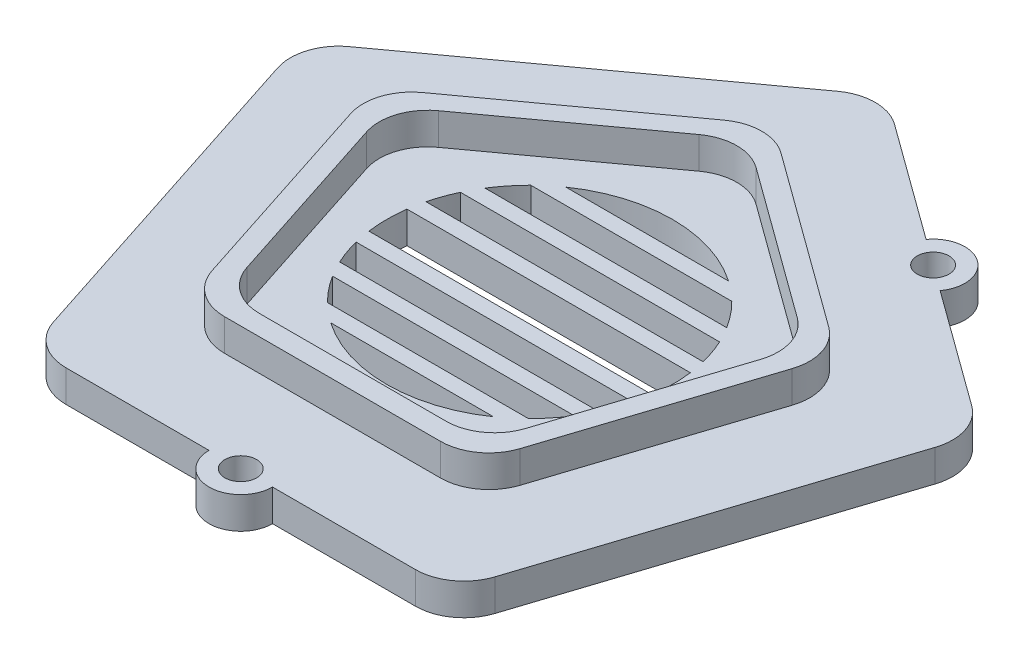
SolidWorks part; units mm, degrees
material "ABS"
ref_plane "Front Plane" through (0, 0, 0) normal (0, 0, 1) x (1, 0, 0)
ref_plane "Top Plane" through (0, 0, 0) normal (0, 1, 0) x (1, 0, 0)
ref_plane "Right Plane" through (0, 0, 0) normal (1, 0, 0) x (0, 0, -1)
sketch "Sketch1" plane through (0, 0, 0) normal (0, 1, 0) x (1, 0, 0)
  line L0 (-12.5926, 0) -> (122.24, 0) construction
  line L1 (-76.5046, 8.789) -> (-56.7275, -52.0787)
  line L2 (-32, -70.0442) -> (32, -70.0442)
  line L3 (56.7275, -52.0787) -> (76.5046, 8.789)
  line L4 (67.0595, 37.8578) -> (15.2824, 75.4761)
  line L5 (-15.2824, 75.4761) -> (-67.0595, 37.8578)
  line L7 (-72.7662, 7.5743) -> (-54.4171, -48.8987)
  line L8 (-29.6896, -66.8642) -> (29.6896, -66.8642)
  line L9 (54.4171, -48.8987) -> (72.7662, 7.5743)
  line L10 (63.3212, 36.6432) -> (15.2824, 71.5454)
  line L11 (-15.2824, 71.5454) -> (-63.3212, 36.6432)
  line L12 (-39.9799, 8.2808) -> (-27.4771, -30.1989)
  line L13 (-20.23, -35.4642) -> (20.23, -35.4642)
  line L14 (27.4771, -30.1989) -> (39.9799, 8.2808)
  line L15 (37.2118, 16.8002) -> (4.4789, 40.582)
  line L16 (-4.4789, 40.582) -> (-37.2118, 16.8002)
  line L17 (-34.7536, 6.5827) -> (-24.2471, -25.7532)
  line L18 (-17, -31.0185) -> (17, -31.0185)
  line L19 (24.2471, -25.7532) -> (34.7536, 6.5827)
  line L20 (31.9855, 15.1021) -> (4.4789, 35.0868)
  line L21 (-4.4789, 35.0868) -> (-31.9855, 15.1021)
  line L22 (-31.0153, 5.3681) -> (-21.9366, -22.5732)
  line L23 (-14.6896, -27.8385) -> (14.6896, -27.8385)
  line L24 (21.9366, -22.5732) -> (31.0153, 5.3681)
  line L25 (28.2472, 13.8875) -> (4.4789, 31.1561)
  line L26 (-4.4789, 31.1561) -> (-28.2472, 13.8875)
  circle A0 centre (0, 0) radius 70.0442 construction
  arc A1 (-56.7275, -52.0787) -> (-32, -70.0442) centre (-32, -44.0442) ccw
  arc A2 (32, -70.0442) -> (56.7275, -52.0787) centre (32, -44.0442) ccw
  arc A3 (76.5046, 8.789) -> (67.0595, 37.8578) centre (51.7771, 16.8234) ccw
  arc A4 (15.2824, 75.4761) -> (-15.2824, 75.4761) centre (0, 54.4417) ccw
  arc A5 (-76.5046, 8.789) -> (-67.0595, 37.8578) centre (-51.7771, 16.8234) cw
  circle A6 centre (0, 0) radius 66.8642 construction
  arc A7 (15.2824, 71.5454) -> (-15.2824, 71.5454) centre (0, 50.511) ccw
  arc A8 (72.7662, 7.5743) -> (63.3212, 36.6432) centre (48.0388, 15.6087) ccw
  arc A9 (29.6896, -66.8642) -> (54.4171, -48.8987) centre (29.6896, -40.8642) ccw
  arc A10 (-72.7662, 7.5743) -> (-63.3212, 36.6432) centre (-48.0388, 15.6087) cw
  arc A11 (-54.4171, -48.8987) -> (-29.6896, -66.8642) centre (-29.6896, -40.8642) ccw
  circle A12 centre (0, 0) radius 35.4642 construction
  circle A13 centre (0, 0) radius 31.0185 construction
  arc A14 (-24.2471, -25.7532) -> (-17, -31.0185) centre (-17, -23.3985) ccw
  arc A15 (17, -31.0185) -> (24.2471, -25.7532) centre (17, -23.3985) ccw
  arc A16 (34.7536, 6.5827) -> (31.9855, 15.1021) centre (27.5066, 8.9374) ccw
  arc A17 (4.4789, 35.0868) -> (-4.4789, 35.0868) centre (0, 28.9221) ccw
  arc A18 (4.4789, 40.582) -> (-4.4789, 40.582) centre (0, 34.4173) ccw
  arc A19 (39.9799, 8.2808) -> (37.2118, 16.8002) centre (32.7328, 10.6355) ccw
  arc A20 (20.23, -35.4642) -> (27.4771, -30.1989) centre (20.23, -27.8442) ccw
  arc A21 (-27.4771, -30.1989) -> (-20.23, -35.4642) centre (-20.23, -27.8442) ccw
  arc A22 (-39.9799, 8.2808) -> (-37.2118, 16.8002) centre (-32.7328, 10.6355) cw
  arc A23 (-34.7536, 6.5827) -> (-31.9855, 15.1021) centre (-27.5066, 8.9374) cw
  circle A24 centre (0, 0) radius 27.8385 construction
  arc A25 (-21.9366, -22.5732) -> (-14.6896, -27.8385) centre (-14.6896, -20.2185) ccw
  arc A26 (14.6896, -27.8385) -> (21.9366, -22.5732) centre (14.6896, -20.2185) ccw
  arc A27 (31.0153, 5.3681) -> (28.2472, 13.8875) centre (23.7683, 7.7228) ccw
  arc A28 (4.4789, 31.1561) -> (-4.4789, 31.1561) centre (0, 24.9914) ccw
  arc A29 (-31.0153, 5.3681) -> (-28.2472, 13.8875) centre (-23.7683, 7.7228) cw
  dimension "D1" = 26
  dimension "D3" = 26
  dimension "D5" = 7.62
  dimension "D8" = 7.62
  dimension "D2" = 64
  dimension "D4" = 3.18
  dimension "D6" = 40.46
  dimension "D7" = 34
  dimension "D9" = 3.18
extrude "Boss-Extrude1" add sketch "Sketch1" along normal blind 10 contours A23 L17 A14 L18 A15 L19 A16 L20 A17 L21 L22 A29 L26 A28 L25 A27 L24 A26 L23 A25 region at (-33.8267, 0, -10.9909)
sketch "Sketch2" plane through (0, 0, 0) normal (0, -1, 0) x (1, 0, 0)
  line L15 (-54.4171, 48.8987) -> (-72.7662, -7.5743)
  line L16 (29.6896, 66.8642) -> (-29.6896, 66.8642)
  line L17 (72.7662, -7.5743) -> (54.4171, 48.8987)
  line L18 (15.2824, -71.5454) -> (63.3212, -36.6432)
  line L19 (-63.3212, -36.6432) -> (-15.2824, -71.5454)
  line L20 (-54.4171, 48.8987) -> (-72.7662, -7.5743)
  line L21 (29.6896, 66.8642) -> (-29.6896, 66.8642)
  line L22 (72.7662, -7.5743) -> (54.4171, 48.8987)
  line L23 (15.2824, -71.5454) -> (63.3212, -36.6432)
  line L24 (-63.3212, -36.6432) -> (-15.2824, -71.5454)
  line L25 (-24.2471, 25.7532) -> (-34.7536, -6.5827)
  line L26 (17, 31.0185) -> (-17, 31.0185)
  line L27 (34.7536, -6.5827) -> (24.2471, 25.7532)
  line L28 (4.4789, -35.0868) -> (31.9855, -15.1021)
  line L29 (-31.9855, -15.1021) -> (-4.4789, -35.0868)
  line L30 (-24.2471, 25.7532) -> (-34.7536, -6.5827)
  line L31 (17, 31.0185) -> (-17, 31.0185)
  line L32 (34.7536, -6.5827) -> (24.2471, 25.7532)
  line L33 (4.4789, -35.0868) -> (31.9855, -15.1021)
  line L34 (-31.9855, -15.1021) -> (-4.4789, -35.0868)
  line L35 (-27.4771, 30.1989) -> (-39.9799, -8.2808)
  line L36 (20.23, 35.4642) -> (-20.23, 35.4642)
  line L37 (39.9799, -8.2808) -> (27.4771, 30.1989)
  line L38 (4.4789, -40.582) -> (37.2118, -16.8002)
  line L39 (-37.2118, -16.8002) -> (-4.4789, -40.582)
  line L40 (-27.4771, 30.1989) -> (-39.9799, -8.2808)
  line L41 (20.23, 35.4642) -> (-20.23, 35.4642)
  line L42 (39.9799, -8.2808) -> (27.4771, 30.1989)
  line L43 (4.4789, -40.582) -> (37.2118, -16.8002)
  line L44 (-37.2118, -16.8002) -> (-4.4789, -40.582)
  line L45 (-21.9366, 22.5732) -> (-31.0153, -5.3681)
  line L46 (14.6896, 27.8385) -> (-14.6896, 27.8385)
  line L47 (31.0153, -5.3681) -> (21.9366, 22.5732)
  line L48 (4.4789, -31.1561) -> (28.2472, -13.8875)
  line L49 (-28.2472, -13.8875) -> (-4.4789, -31.1561)
  line L50 (-21.9366, 22.5732) -> (-31.0153, -5.3681)
  line L51 (14.6896, 27.8385) -> (-14.6896, 27.8385)
  line L52 (31.0153, -5.3681) -> (21.9366, 22.5732)
  line L53 (4.4789, -31.1561) -> (28.2472, -13.8875)
  line L54 (-28.2472, -13.8875) -> (-4.4789, -31.1561)
  arc A15 (-29.6896, 66.8642) -> (-54.4171, 48.8987) centre (-29.6896, 40.8642) ccw
  arc A16 (54.4171, 48.8987) -> (29.6896, 66.8642) centre (29.6896, 40.8642) ccw
  arc A17 (63.3212, -36.6432) -> (72.7662, -7.5743) centre (48.0388, -15.6087) ccw
  arc A18 (-15.2824, -71.5454) -> (15.2824, -71.5454) centre (0, -50.511) ccw
  arc A19 (-72.7662, -7.5743) -> (-63.3212, -36.6432) centre (-48.0388, -15.6087) ccw
  arc A20 (-29.6896, 66.8642) -> (-54.4171, 48.8987) centre (-29.6896, 40.8642) ccw
  arc A21 (54.4171, 48.8987) -> (29.6896, 66.8642) centre (29.6896, 40.8642) ccw
  arc A22 (63.3212, -36.6432) -> (72.7662, -7.5743) centre (48.0388, -15.6087) ccw
  arc A23 (-15.2824, -71.5454) -> (15.2824, -71.5454) centre (0, -50.511) ccw
  arc A24 (-72.7662, -7.5743) -> (-63.3212, -36.6432) centre (-48.0388, -15.6087) ccw
  arc A25 (-17, 31.0185) -> (-24.2471, 25.7532) centre (-17, 23.3985) ccw
  arc A26 (24.2471, 25.7532) -> (17, 31.0185) centre (17, 23.3985) ccw
  arc A27 (31.9855, -15.1021) -> (34.7536, -6.5827) centre (27.5066, -8.9374) ccw
  arc A28 (-4.4789, -35.0868) -> (4.4789, -35.0868) centre (0, -28.9221) ccw
  arc A29 (-34.7536, -6.5827) -> (-31.9855, -15.1021) centre (-27.5066, -8.9374) ccw
  arc A30 (-17, 31.0185) -> (-24.2471, 25.7532) centre (-17, 23.3985) ccw
  arc A31 (24.2471, 25.7532) -> (17, 31.0185) centre (17, 23.3985) ccw
  arc A32 (31.9855, -15.1021) -> (34.7536, -6.5827) centre (27.5066, -8.9374) ccw
  arc A33 (-4.4789, -35.0868) -> (4.4789, -35.0868) centre (0, -28.9221) ccw
  arc A34 (-34.7536, -6.5827) -> (-31.9855, -15.1021) centre (-27.5066, -8.9374) ccw
  arc A35 (-20.23, 35.4642) -> (-27.4771, 30.1989) centre (-20.23, 27.8442) ccw
  arc A36 (27.4771, 30.1989) -> (20.23, 35.4642) centre (20.23, 27.8442) ccw
  arc A37 (37.2118, -16.8002) -> (39.9799, -8.2808) centre (32.7328, -10.6355) ccw
  arc A38 (-4.4789, -40.582) -> (4.4789, -40.582) centre (0, -34.4173) ccw
  arc A39 (-39.9799, -8.2808) -> (-37.2118, -16.8002) centre (-32.7328, -10.6355) ccw
  arc A40 (-20.23, 35.4642) -> (-27.4771, 30.1989) centre (-20.23, 27.8442) ccw
  arc A41 (27.4771, 30.1989) -> (20.23, 35.4642) centre (20.23, 27.8442) ccw
  arc A42 (37.2118, -16.8002) -> (39.9799, -8.2808) centre (32.7328, -10.6355) ccw
  arc A43 (-4.4789, -40.582) -> (4.4789, -40.582) centre (0, -34.4173) ccw
  arc A44 (-39.9799, -8.2808) -> (-37.2118, -16.8002) centre (-32.7328, -10.6355) ccw
  arc A45 (-14.6896, 27.8385) -> (-21.9366, 22.5732) centre (-14.6896, 20.2185) ccw
  arc A46 (21.9366, 22.5732) -> (14.6896, 27.8385) centre (14.6896, 20.2185) ccw
  arc A47 (28.2472, -13.8875) -> (31.0153, -5.3681) centre (23.7683, -7.7228) ccw
  arc A48 (-4.4789, -31.1561) -> (4.4789, -31.1561) centre (0, -24.9914) ccw
  arc A49 (-31.0153, -5.3681) -> (-28.2472, -13.8875) centre (-23.7683, -7.7228) ccw
  arc A50 (-14.6896, 27.8385) -> (-21.9366, 22.5732) centre (-14.6896, 20.2185) ccw
  arc A51 (21.9366, 22.5732) -> (14.6896, 27.8385) centre (14.6896, 20.2185) ccw
  arc A52 (28.2472, -13.8875) -> (31.0153, -5.3681) centre (23.7683, -7.7228) ccw
  arc A53 (-4.4789, -31.1561) -> (4.4789, -31.1561) centre (0, -24.9914) ccw
  arc A54 (-31.0153, -5.3681) -> (-28.2472, -13.8875) centre (-23.7683, -7.7228) ccw
  arc M51 (-34.7536, -6.5827) -> (-31.9855, -15.1021) centre (-27.5066, -8.9374) ccw
  line M52 (-31.9855, -15.1021) -> (-4.4789, -35.0868)
  arc M53 (-4.4789, -35.0868) -> (4.4789, -35.0868) centre (0, -28.9221) ccw
  line M54 (4.4789, -35.0868) -> (31.9855, -15.1021)
  arc M55 (31.9855, -15.1021) -> (34.7536, -6.5827) centre (27.5066, -8.9374) ccw
  line M56 (34.7536, -6.5827) -> (24.2471, 25.7532)
  arc M57 (24.2471, 25.7532) -> (17, 31.0185) centre (17, 23.3985) ccw
  line M58 (17, 31.0185) -> (-17, 31.0185)
  arc M59 (-17, 31.0185) -> (-24.2471, 25.7532) centre (-17, 23.3985) ccw
  line M60 (-24.2471, 25.7532) -> (-34.7536, -6.5827)
  line M61 (-31.0153, -5.3681) -> (-21.9366, 22.5732)
  arc M62 (-21.9366, 22.5732) -> (-14.6896, 27.8385) centre (-14.6896, 20.2185) cw
  line M63 (-14.6896, 27.8385) -> (14.6896, 27.8385)
  arc M64 (14.6896, 27.8385) -> (21.9366, 22.5732) centre (14.6896, 20.2185) cw
  line M65 (21.9366, 22.5732) -> (31.0153, -5.3681)
  arc M66 (31.0153, -5.3681) -> (28.2472, -13.8875) centre (23.7683, -7.7228) cw
  line M67 (28.2472, -13.8875) -> (4.4789, -31.1561)
  arc M68 (4.4789, -31.1561) -> (-4.4789, -31.1561) centre (0, -24.9914) cw
  line M69 (-4.4789, -31.1561) -> (-28.2472, -13.8875)
  arc M70 (-28.2472, -13.8875) -> (-31.0153, -5.3681) centre (-23.7683, -7.7228) cw
  dimension "D2" = 0
  dimension "D3" = 0
  dimension "D4" = 0
  dimension "D5" = 0
extrude "Boss-Extrude2" add sketch "Sketch2" against normal blind 5 contours L20 A24 L24 A23 L23 A22 L22 A21 L21 A20 A44 L40 A40 L41 A41 L42 A42 L43 A43 L44 | A24 L20 A20 L21 A21 L22 A22 L23 A23 L24 | M61 M70 M69 M68 M67 M66 M65 M64 M63 M62 | L40 A44 L44 A43 L43 A42 L42 A41 L41 A40 M51 M60 M59 M58 M57 M56 M55 M54 M53 M52 region at (-43.7605, 0, 60.2312) region at (-24.0512, 0, 33.1037) region at (0, 0, 0)
sketch "Sketch4" plane through (0, 5, 0) normal (0, 1, 0) x (1, 0, 0)
  line L5 (-15.2824, 71.5454) -> (-63.3212, 36.6432)
  line L6 (63.3212, 36.6432) -> (15.2824, 71.5454)
  line L7 (54.4171, -48.8987) -> (72.7662, 7.5743)
  line L8 (-29.6896, -66.8642) -> (29.6896, -66.8642)
  line L9 (-72.7662, 7.5743) -> (-54.4171, -48.8987)
  line L11 (63.3212, 36.6432) -> (39.3018, 54.0943)
  line L12 (54.4171, -48.8987) -> (72.7662, 7.5743)
  line L13 (0, -66.8642) -> (29.6896, -66.8642)
  line L18 (-51.7424, 12.1027) -> (-34.7467, -40.2047)
  line L27 (-27.4996, -45.47) -> (27.4996, -45.47)
  line L29 (34.7467, -40.2047) -> (51.7424, 12.1027)
  line L37 (48.9743, 20.6221) -> (4.4789, 52.9499)
  line L46 (-4.4789, 52.9499) -> (-48.9743, 20.6221)
  line L47 (-54.4171, -48.8987) -> (-72.7662, 7.5743) construction
  line L48 (-63.3212, 36.6432) -> (-15.2824, 71.5454) construction
  line L49 (-54.4171, -48.8987) -> (-72.7662, 7.5743)
  line L50 (-63.3212, 36.6432) -> (-15.2824, 71.5454)
  line L51 (39.3018, 54.0943) -> (15.2824, 71.5454)
  line L52 (-29.6896, -66.8642) -> (0, -66.8642)
  circle A0 centre (0, 0) radius 45.47 construction
  arc A5 (15.2824, 71.5454) -> (-15.2824, 71.5454) centre (0, 50.511) ccw
  arc A6 (72.7662, 7.5743) -> (63.3212, 36.6432) centre (48.0388, 15.6087) ccw
  arc A7 (29.6896, -66.8642) -> (54.4171, -48.8987) centre (29.6896, -40.8642) ccw
  arc A8 (-54.4171, -48.8987) -> (-29.6896, -66.8642) centre (-29.6896, -40.8642) ccw
  arc A9 (-63.3212, 36.6432) -> (-72.7662, 7.5743) centre (-48.0388, 15.6087) ccw
  arc A11 (72.7662, 7.5743) -> (63.3212, 36.6432) centre (48.0388, 15.6087) ccw
  arc A12 (29.6896, -66.8642) -> (54.4171, -48.8987) centre (29.6896, -40.8642) ccw
  arc A19 (-51.7424, 12.1027) -> (-48.9743, 20.6221) centre (-44.4953, 14.4574) cw
  arc A25 (-34.7467, -40.2047) -> (-27.4996, -45.47) centre (-27.4996, -37.85) ccw
  arc A26 (27.4996, -45.47) -> (34.7467, -40.2047) centre (27.4996, -37.85) ccw
  arc A28 (51.7424, 12.1027) -> (48.9743, 20.6221) centre (44.4953, 14.4574) ccw
  arc A35 (4.4789, 52.9499) -> (-4.4789, 52.9499) centre (0, 46.7852) ccw
  arc A46 (-54.4171, -48.8987) -> (-29.6896, -66.8642) centre (-29.6896, -40.8642) ccw construction
  arc A47 (-63.3212, 36.6432) -> (-72.7662, 7.5743) centre (-48.0388, 15.6087) ccw construction
  arc A48 (15.2824, 71.5454) -> (-15.2824, 71.5454) centre (0, 50.511) ccw construction
  arc A49 (-54.4171, -48.8987) -> (-29.6896, -66.8642) centre (-29.6896, -40.8642) ccw
  arc A50 (-63.3212, 36.6432) -> (-72.7662, 7.5743) centre (-48.0388, 15.6087) ccw
  arc A51 (15.2824, 71.5454) -> (-15.2824, 71.5454) centre (0, 50.511) ccw
  line M41 (-72.7662, 7.5743) -> (-54.4171, -48.8987)
  arc M42 (-54.4171, -48.8987) -> (-29.6896, -66.8642) centre (-29.6896, -40.8642) ccw
  line M43 (-29.6896, -66.8642) -> (29.6896, -66.8642)
  line M47 (63.3212, 36.6432) -> (15.2824, 71.5454)
  arc M48 (15.2824, 71.5454) -> (-15.2824, 71.5454) centre (0, 50.511) ccw
  line M49 (-15.2824, 71.5454) -> (-63.3212, 36.6432)
  arc M50 (-63.3212, 36.6432) -> (-72.7662, 7.5743) centre (-48.0388, 15.6087) ccw
  dimension "D3" = 7.62
  dimension "D2" = 45.47
  dimension "D1" = 0
extrude "Cut-Extrude1" cut sketch "Sketch4" against normal through all contours M47 M48 M49 M50 M41 M42 M43 region at (0, 5, -74.4498)
ref_plane "Plane4" through (-51.7424, 5, -12.1027) normal (0.309, 0, 0.9511) x (0.9511, 0, -0.309)
sketch "Sketch6" plane through (0, 5, 0) normal (0, 1, 0) x (1, 0, 0)
  line L7 (63.5917, -20.6622) -> (-51.7406, 16.8115) construction
  circle A7 centre (26.7257, 36.7848) radius 4
  circle A8 centre (26.7257, 36.7848) radius 2.5
  circle A9 centre (0, -45.4685) radius 2.5
  circle A10 centre (0, -45.4685) radius 4
  point P2 (0, 0)
  point P5 (0, 0)
  point P6 (0, 0)
  point P11 (0, 0)
  point P12 (0, 0)
sketch "Sketch7" plane through (0, 5, 0) normal (0, 1, 0) x (1, 0, 0)
  line L0 (-12.8062, -18.5) -> (12.8062, -18.5)
  line L1 (22.5, -22.5) -> (-22.5, -22.5)
  line L2 (22.5, -22.5) -> (22.5, 22.5)
  line L3 (22.5, 22.5) -> (-22.5, 22.5)
  line L4 (-22.5, -22.5) -> (-22.5, 22.5)
  line L5 (22.5, -22.5) -> (-22.5, 22.5) construction
  line L6 (22.5, 22.5) -> (-22.5, -22.5) construction
  line L7 (15.8193, -16) -> (-15.8193, -16)
  line L8 (22.5, 0) -> (-22.5, 0) construction
  line L9 (-19.0329, -12) -> (19.0329, -12)
  line L10 (20.3961, -9.5) -> (-20.3961, -9.5)
  line L11 (21.8174, -5.5) -> (-21.8174, -5.5)
  line L12 (22.2991, -3) -> (-22.2991, -3)
  line L13 (22.2991, 3) -> (-22.2991, 3)
  line L14 (15.8193, 16) -> (-15.8193, 16)
  line L15 (-12.8062, 18.5) -> (12.8062, 18.5)
  line L16 (-19.0329, 12) -> (19.0329, 12)
  line L17 (20.3961, 9.5) -> (-20.3961, 9.5)
  line L18 (21.8174, 5.5) -> (-21.8174, 5.5)
  line L19 (63.5917, -20.6622) -> (-51.7406, 16.8115) construction
  circle A0 centre (0, 0) radius 22.5
  circle A3 centre (0, -45.4685) radius 4
  circle A5 centre (26.7257, 36.7848) radius 2.5
  circle A7 centre (0, -45.4685) radius 2.5
  circle A9 centre (26.7257, 36.7848) radius 4
  point P4 (0, 0)
  point P5 (0, 0)
  point P8 (0, 0)
  point P9 (0, 0)
  point P10 (0, 0)
  point P12 (0, 0)
  point P13 (0, 0)
  point P45 (0, 0)
  dimension "D5" = 45
  dimension "D6" = 2.5
  dimension "D7" = 4
  dimension "D8" = 4
  dimension "D9" = 2.5
  dimension "D10" = 4
  dimension "D11" = 2.5
extrude "Cut-Extrude2" cut sketch "Sketch7" against normal up to surface (5 mm away) contours L7 A0 L9 | L10 A0 L11 | L12 A0 L13 | L18 A0 L17 | L16 A0 L14 | L15 A0 | A0 L0 | A5 | A7 region at (0, 5, 20.1129) region at (0, 5, 13.9392) region at (0, 5, 7.4777) region at (0, 5, 0) region at (0, 5, -20.1129) region at (0, 5, -7.4777) region at (0, 5, -13.9392) region at (26.7257, 5, -36.7848) up to face at (0, 0, 0)
extrude "Boss-Extrude4" add sketch "Sketch6" against normal up to surface (5 mm away) up to face at (0, 0, 0)
sketch "Sketch8" plane through (0, 5, 0) normal (0, 1, 0) x (1, 0, 0)
  line L0 (-27.4996, -45.47) -> (-4, -45.47) construction
  line L1 (4, -45.47) -> (27.4996, -45.47) construction
  line L2 (-4, -45.47) -> (-5, -45.47)
  line L3 (5, -45.47) -> (4, -45.47)
  line L4 (43.2445, -14.051) -> (-51.7424, 16.8121) construction
  line L5 (34.7467, -40.2047) -> (51.7424, 12.1027) construction
  line L6 (23.4905, 39.1371) -> (22.6815, 39.7249)
  line L7 (30.7717, 33.8471) -> (29.9627, 34.4349)
  arc A0 (-5, -45.47) -> (5, -45.47) centre (0, -45.4685) ccw
  arc A1 (-4, -45.47) -> (4, -45.47) centre (0, -45.4685) ccw
  arc A2 (-48.9743, 20.6221) -> (-51.7424, 12.1027) centre (-44.4953, 14.4574) ccw construction
  arc A3 (23.4905, 39.1371) -> (29.9627, 34.4349) centre (26.7257, 36.7848) cw
  arc A4 (22.6815, 39.7249) -> (30.7717, 33.8471) centre (26.7257, 36.7848) cw
  dimension "D1" = 5
extrude "Boss-Extrude5" add sketch "Sketch8" against normal blind 5
